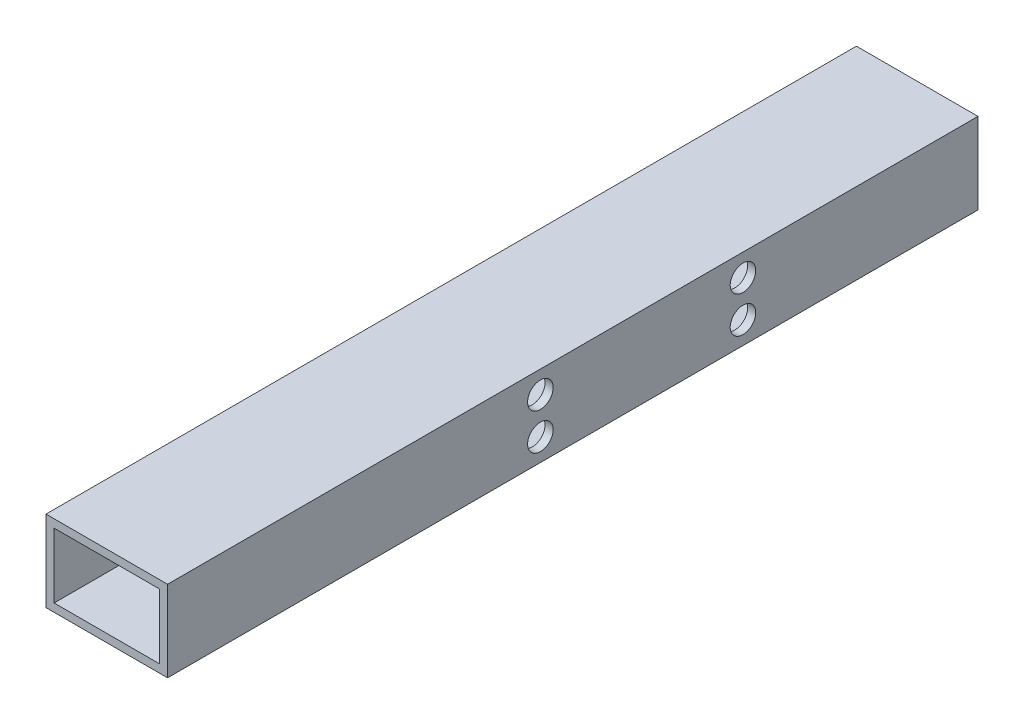
SolidWorks part; units mm, degrees
ref_plane "Спереди" through (0, 0, 0) normal (0, 0, 1) x (1, 0, 0)
ref_plane "Сверху" through (0, 0, 0) normal (0, 1, 0) x (1, 0, 0)
ref_plane "Справа" through (0, 0, 0) normal (1, 0, 0) x (0, 0, -1)
sketch "Эскиз1" plane through (0, 0, 0) normal (0, 0, 1) x (1, 0, 0)
  line L0 (-15, 10) -> (15, 10)
  line L1 (-13, -8) -> (13, -8)
  line L2 (-13, -8) -> (-13, 8)
  line L3 (-13, 8) -> (13, 8)
  line L4 (13, -8) -> (13, 8)
  line L5 (-13, -8) -> (13, 8) construction
  line L6 (-13, 8) -> (13, -8) construction
  line L7 (15, -10) -> (15, 10)
  line L8 (-15, -10) -> (15, -10)
  line L9 (-15, -10) -> (-15, 10)
  point P0 (0, 0)
  dimension "D2" = 20
  dimension "D3" = 30
  dimension "D1" = 2
extrude "Бобышка-Вытянуть1" add sketch "Эскиз1" along normal blind 200
sketch "Эскиз2" plane through (15, 0, 0) normal (1, 0, 0) x (0, 0, -1)
  line L0 (-200, -10) -> (0, -10) construction
  line L1 (-200, 10) -> (0, 10) construction
  line L2 (0, -10) -> (0, 10) construction
  circle A0 centre (-108, 4.5) radius 1.6
  circle A1 centre (-108, -4.5) radius 1.6
  circle A2 centre (-58, -4.5) radius 1.6
  circle A3 centre (-58, 4.5) radius 1.6
  circle A4 centre (-108, -4.5) radius 3.15
  circle A5 centre (-108, 4.5) radius 3.15
  circle A6 centre (-58, -4.5) radius 3.15
  circle A7 centre (-58, 4.5) radius 3.15
  dimension "D1" = 3.2
  dimension "D2" = 6.3
  dimension "D5" = 50
  dimension "D3" = 5.5
  dimension "D4" = 5.5
  dimension "D6" = 58
extrude "Вырез-Вытянуть1" cut sketch "Эскиз2" against normal through all contours A2 | A3 | A0 | A1 region at (15, 4.5, 108) region at (15, -4.5, 108) region at (15, -4.5, 58) region at (15, 4.5, 58)
extrude "Вырез-Вытянуть2" cut sketch "Эскиз2<3>" against normal blind 3
sketch "Эскиз2<3>" plane through (15, 0, 0) normal (1, 0, 0) x (0, 0, -1) same geometry as "Эскиз2"
